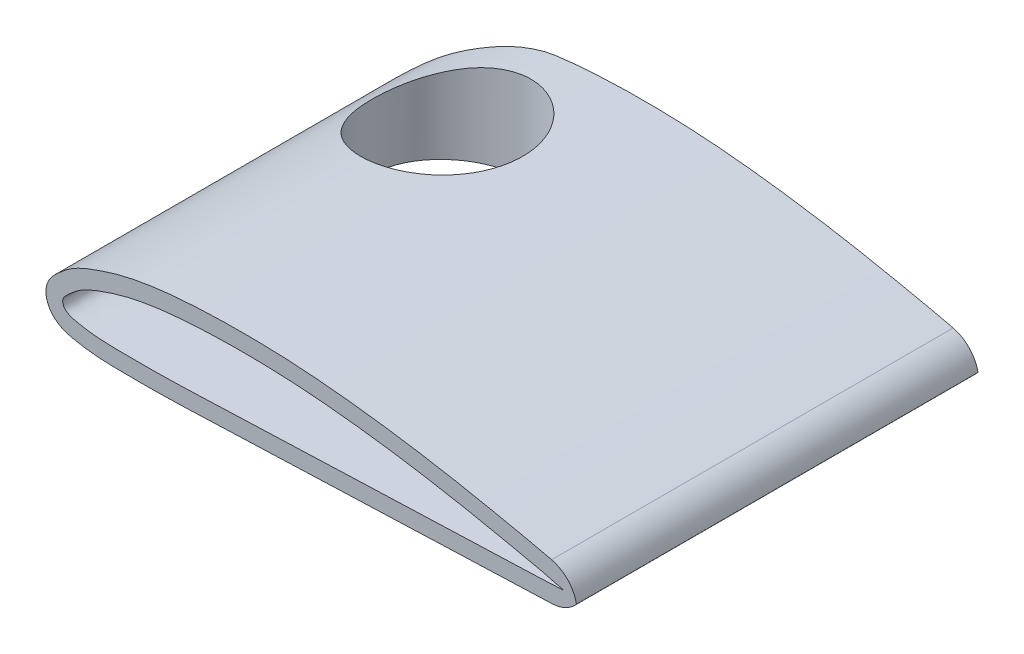
SolidWorks part; units mm, degrees
note: The reader was unsure of these and kept them because the rebuilt part matched: shared geometry of "Sketch4<2>".
ref_plane "Ön Düzlem" through (0, 0, 0) normal (0, 0, 1) x (1, 0, 0)
ref_plane "Üst Düzlem" through (0, 0, 0) normal (0, 1, 0) x (1, 0, 0)
ref_plane "Sağ Düzlem" through (0, 0, 0) normal (1, 0, 0) x (0, 0, -1)
sketch "Sketch1" plane through (0, 0, 0) normal (0, 0, 1) x (1, 0, 0)
  line L0 (273.8644, 129.7584) -> (1369.8644, 129.7584) construction
  line L1 (149.8581, 0) -> (149.8558, -0.0087)
  line L2 (155.9643, 3.5657) -> (153.7663, -4.8024)
  spline S0 degree 3 poles (149.8581, 0) (148.0649, 0.471) (143.2248, 1.7424) (133.1757, 3.886) (119.4995, 6.7583) (102.5414, 9.7444) (85.9645, 11.9563) (70.8168, 13.3138) (56.6678, 13.8481) (41.7647, 13.6427) (27.8783, 12.5388) (17.5169, 10.3502) (10.936, 8.1212) (5.6282, 6.0173) (2.2408, 3.1599) (-0.2937, 0.7197) (0.5423, -2.4008) (4.9566, -3.5377) (10.6122, -4.3278) (18.7708, -4.4982) (30.5005, -4.4934) (45.7845, -3.9122) (66.3708, -3.1228) (87.0163, -2.3781) (108.488, -1.5762) (124.5472, -1.0028) (137.7849, -0.5219) (145.1223, -0.2664) (148.9169, -0.06) (149.8558, -0.0087) knots 0 0 0 0 0.018163 0.049023 0.100644 0.15508 0.217678 0.264436 0.304025 0.356345 0.410393 0.440307 0.459596 0.478843 0.494821 0.504999 0.508601 0.524256 0.542616 0.567477 0.602874 0.658123 0.717036 0.804816 0.860487 0.927555 0.96225 0.990269 0.999481 0.999481 0.999481 0.999481
  spline S1 degree 1 poles (155.9643, 3.5657) (153.7663, -4.8024) knots 0 0 1 1 construction
  spline S2 degree 3 poles (155.9643, 3.5657) (154.3789, 3.9821) (151.2214, 4.8106) (146.4053, 6.0796) (141.4592, 7.231) (136.6165, 8.2623) (131.8023, 9.2806) (125.348, 10.622) (117.2296, 12.2227) (107.436, 13.9393) (97.5987, 15.4408) (87.7223, 16.7063) (77.8097, 17.7331) (67.8079, 18.447) (57.7939, 18.7732) (47.7698, 18.7355) (39.4274, 18.4012) (32.6805, 17.8783) (27.5943, 17.2987) (22.4892, 16.4892) (18.2218, 15.5713) (14.817, 14.6458) (12.3108, 13.8604) (9.8671, 13.0078) (7.4153, 12.102) (5.1995, 11.1503) (3.4062, 10.1987) (2.0681, 9.3602) (0.8539, 8.4728) (-0.2716, 7.5539) (-1.1738, 6.7528) (-1.8463, 6.1385) (-2.5103, 5.5088) (-3.2938, 4.6501) (-4.14, 3.4467) (-4.7575, 1.9999) (-5.006, 0.5771) (-5.0045, -0.9474) (-4.6414, -2.46) (-3.865, -4.0582) (-2.7961, -5.3678) (-1.2429, -6.6358) (0.6171, -7.5095) (2.5072, -8.0359) (3.9575, -8.3344) (5.3338, -8.5928) (6.6822, -8.8045) (8.4438, -9.0334) (10.6183, -9.23) (13.2248, -9.3643) (15.8027, -9.4307) (18.317, -9.4626) (21.6435, -9.4888) (25.784, -9.4833) (30.7543, -9.4112) (35.716, -9.2795) (40.6638, -9.1103) (47.2322, -8.8598) (55.417, -8.5465) (65.237, -8.1755) (75.0605, -7.8138) (84.8885, -7.4554) (97.9978, -6.9718) (114.3642, -6.3678) (129.1179, -5.8389) (138.9321, -5.4857) (143.8593, -5.3146) (148.8723, -5.0773) (152.1278, -4.8919) (153.7663, -4.8024) knots -0.016327 -0.016327 -0.016327 -0.016327 -0.000269 0.015789 0.031847 0.047904 0.063962 0.08002 0.112136 0.144252 0.176368 0.208483 0.240599 0.272715 0.304831 0.336947 0.369062 0.38512 0.401178 0.417236 0.433294 0.441323 0.449352 0.457381 0.46541 0.473439 0.477453 0.481468 0.485482 0.489497 0.493511 0.495518 0.497526 0.499533 0.50154 0.503547 0.504551 0.505554 0.507562 0.509569 0.511576 0.513583 0.517598 0.521612 0.525627 0.529641 0.533656 0.53767 0.545699 0.553728 0.561757 0.569786 0.577815 0.593873 0.609931 0.625989 0.642047 0.658105 0.69022 0.722336 0.754452 0.786568 0.818683 0.882915 0.947147 0.963205 0.979262 0.99532 1.011378 1.011378 1.011378 1.011378
  dimension "D1" = 5
extrude "Boss-Extrude1" add sketch "Sketch1" along normal blind 120
sketch "Sketch3" plane through (0, 0, 0) normal (0, 0, -1) x (-1, 0, 0)
  spline S0 degree 3 poles (-11.739, -7.2673) (10.624, -4.9516) (-6.4324, 9.3983) (-25.8806, 15.5562) (-57.6407, 15.4866) (-94.3164, 14.9013) (-121.9554, 9.4163) (-155.6483, 3.7423) (-152.2996, -5.019) (-127.4429, -2.62) (-110.6572, -5.8508) (-70.6754, -4.9517) (-43.155, -7.1816) (-11.739, -7.2673) (10.624, -4.9516) (-6.4324, 9.3983) knots -0.325561 -0.13651 -0.103954 0 0.019859 0.056297 0.104262 0.197907 0.252889 0.30035 0.312342 0.372817 0.481474 0.674439 0.86349 0.896046 1 1.019859 1.056297 1.104262 only from (0.8788, 2.8169) to (0.8788, 2.8169)
extrude "Boss-Extrude2" add sketch "Sketch3" against normal blind 10
sketch "Sketch4" plane through (0, 0, 0) normal (0, 1, 0) x (1, 0, 0)
  line L0 (155.9643, 0) -> (-4.9986, 0) construction
  line L1 (-4.9986, 0) -> (-4.9986, -120) construction
  line L2 (60.0014, 0) -> (60.0014, -65)
  line L3 (60.0014, -65) -> (-4.9986, -65)
  line L4 (-4.9986, -65) -> (-4.9986, 0)
  line L5 (-4.9986, 0) -> (60.0014, 0)
  circle A0 centre (27.5014, -32.5) radius 22.5
  dimension "D1" = 45
  dimension "D2" = 32.5
  dimension "D3" = 32.5
  dimension "D4" = 32.5
  dimension "D5" = 32.5
extrude "Boss-Extrude3" add sketch "Sketch4" along normal up to next and the other way up to next
extrude "Cut-Extrude1" cut sketch "Sketch4<2>" against normal blind 25 and the other way blind 33 contours A0
sketch "Sketch4<2>" plane through (0, 0, 0) normal (0, 1, 0) x (1, 0, 0) same geometry as "Sketch4"
sketch "Sketch5" plane through (0, 0, 0) normal (0, 0, -1) x (-1, 0, 0)
  line L0 (-16.8432, -9.4426) -> (-66.6079, -9.4426) construction
  spline S0 degree 3 poles (-155.9643, 3.5657) (-154.3789, 3.9821) (-151.2214, 4.8106) (-146.4053, 6.0796) (-141.4592, 7.231) (-136.6165, 8.2623) (-131.8023, 9.2806) (-125.348, 10.622) (-117.2296, 12.2227) (-107.436, 13.9393) (-97.5987, 15.4408) (-87.7223, 16.7063) (-77.8097, 17.7331) (-67.8079, 18.447) (-57.7939, 18.7732) (-47.7698, 18.7355) (-39.4274, 18.4012) (-32.6805, 17.8783) (-27.5943, 17.2987) (-22.4892, 16.4892) (-18.2218, 15.5713) (-14.817, 14.6458) (-12.3108, 13.8604) (-9.8671, 13.0078) (-7.4153, 12.102) (-5.1995, 11.1503) (-3.4062, 10.1987) (-2.0681, 9.3602) (-0.8539, 8.4728) (0.2716, 7.5539) (1.1738, 6.7528) (1.8463, 6.1385) (2.5103, 5.5088) (3.2938, 4.6501) (4.14, 3.4467) (4.7575, 1.9999) (5.006, 0.5771) (5.0045, -0.9474) (4.6414, -2.46) (3.865, -4.0582) (2.7961, -5.3678) (1.2429, -6.6358) (-0.6171, -7.5095) (-2.5072, -8.0359) (-3.9575, -8.3344) (-5.3338, -8.5928) (-6.6822, -8.8045) (-8.4438, -9.0334) (-10.6183, -9.23) (-13.2248, -9.3643) (-15.8027, -9.4307) (-18.317, -9.4626) (-21.6435, -9.4888) (-25.784, -9.4833) (-30.7543, -9.4112) (-35.716, -9.2795) (-40.6638, -9.1103) (-47.2322, -8.8598) (-55.417, -8.5465) (-65.237, -8.1755) (-75.0605, -7.8138) (-84.8885, -7.4554) (-97.9978, -6.9718) (-114.3642, -6.3678) (-129.1179, -5.8389) (-138.9321, -5.4857) (-143.8593, -5.3146) (-148.8723, -5.0773) (-152.1278, -4.8919) (-153.7663, -4.8024) knots -0.016327 -0.016327 -0.016327 -0.016327 -0.000269 0.015789 0.031847 0.047904 0.063962 0.08002 0.112136 0.144252 0.176368 0.208483 0.240599 0.272715 0.304831 0.336947 0.369062 0.38512 0.401178 0.417236 0.433294 0.441323 0.449352 0.457381 0.46541 0.473439 0.477453 0.481468 0.485482 0.489497 0.493511 0.495518 0.497526 0.499533 0.50154 0.503547 0.504551 0.505554 0.507562 0.509569 0.511576 0.513583 0.517598 0.521612 0.525627 0.529641 0.533656 0.53767 0.545699 0.553728 0.561757 0.569786 0.577815 0.593873 0.609931 0.625989 0.642047 0.658105 0.69022 0.722336 0.754452 0.786568 0.818683 0.882915 0.947147 0.963205 0.979262 0.99532 1.011378 1.011378 1.011378 1.011378 construction
fillet "Fillet1" radius 10 2 edges at (155.9643, 3.5657, 60) (153.7663, -4.8024, 60)
sketch "Sketch6" plane through (0, 0, 0) normal (0, 1, 0) x (1, 0, 0)
  line L0 (-4.9986, -32.5) -> (-4.9986, 0)
  line L1 (-4.9986, 0) -> (27.5014, 0)
  arc A0 (27.5014, 0) -> (-4.9986, -32.5) centre (27.5014, -32.5) ccw
extrude "Cut-Extrude2" cut sketch "Sketch6" against normal blind 15 and the other way blind 20
